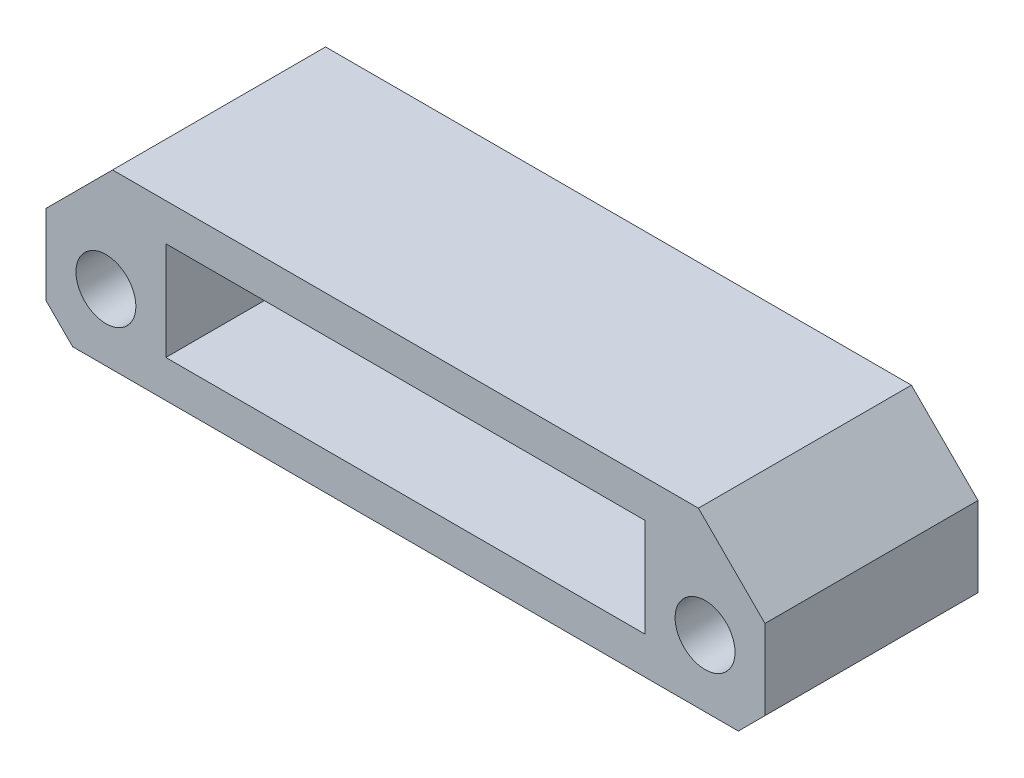
SolidWorks part; units mm, degrees
ref_plane "Front Plane" through (0, 0, 0) normal (0, 0, 1) x (1, 0, 0)
ref_plane "Top Plane" through (0, 0, 0) normal (0, 1, 0) x (1, 0, 0)
ref_plane "Right Plane" through (0, 0, 0) normal (1, 0, 0) x (0, 0, -1)
sketch "Sketch1" plane through (0, 0, 0) normal (0, 0, 1) x (1, 0, 0)
  line L0 (0, 0) -> (0, 13)
  line L1 (0, 13) -> (54, 13)
  line L2 (54, 13) -> (54, 0)
  line L3 (54, 0) -> (45, 0)
  line L5 (45, 10.2) -> (9, 10.2)
  line L7 (9, 0) -> (0, 0)
  line L8 (9, 0) -> (45, 0)
  line L9 (9, 2.8) -> (45, 2.8)
  line L10 (9, 10.2) -> (9, 2.8)
  line L11 (45, 10.2) -> (45, 2.8)
  point P4 (4.5, 0)
  dimension "D1" = 9
  dimension "D2" = 9
  dimension "D3" = 54
  dimension "D4" = 2.8
  dimension "D5" = 10.2
  dimension "D6" = 2.8
extrude "Boss-Extrude1" add sketch "Sketch1" along normal blind 16
chamfer "Chamfer1" distance 2 angle 45 2 edges at (54, 0, 8) (0, 0, 8)
sketch "Sketch2" plane through (0, 0, 16) normal (0, 0, 1) x (1, 0, 0)
  line L0 (2, 0) -> (52, 0) construction
  line L1 (2, 0) -> (52, 0) construction
  circle A0 centre (4.5, 5) radius 2.25
  circle A1 centre (49.5, 5) radius 2.25
  dimension "D5" = 4.5
  dimension "D6" = 4.5
  dimension "D1" = 5
  dimension "D2" = 5
extrude "Cut-Extrude1" cut sketch "Sketch2" against normal blind 16
chamfer "Chamfer3" distance 5 angle 45 2 edges at (54, 13, 8) (0, 13, 8)
